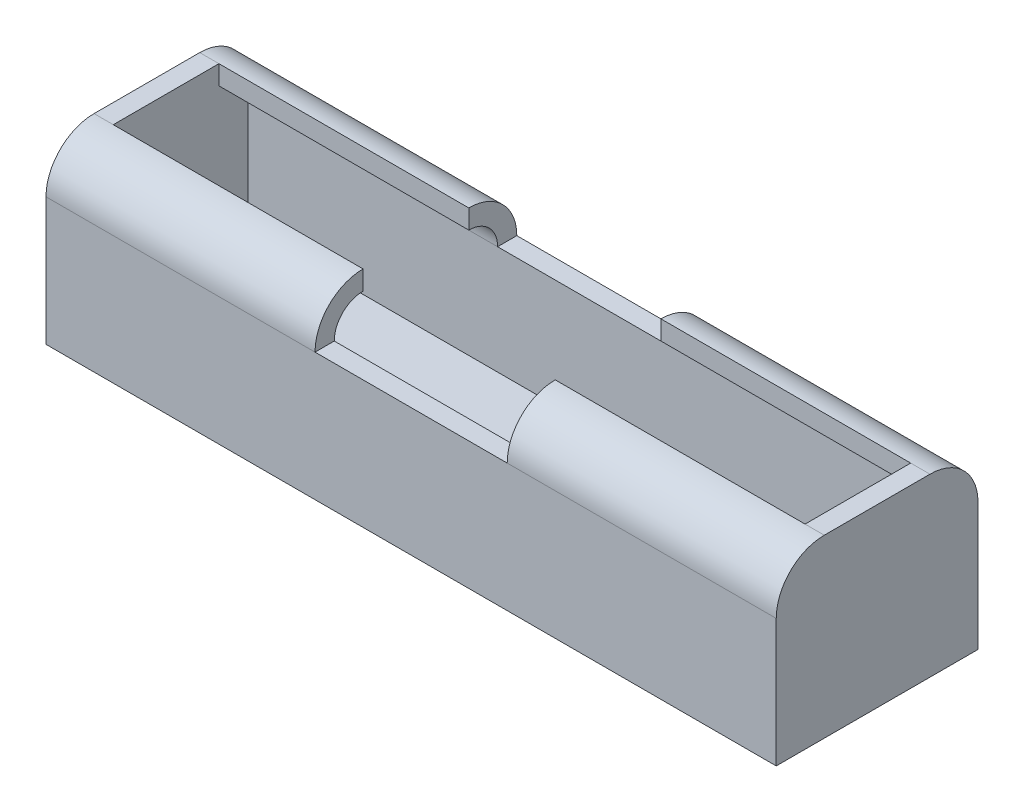
SolidWorks part; units mm, degrees
ref_plane "Front Plane" through (0, 0, 0) normal (0, 0, 1) x (1, 0, 0)
ref_plane "Top Plane" through (0, 0, 0) normal (0, 1, 0) x (1, 0, 0)
ref_plane "Right Plane" through (0, 0, 0) normal (1, 0, 0) x (0, 0, -1)
sketch "Sketch1" plane through (0, 0, 0) normal (1, 0, 0) x (0, 0, -1)
  line L1 (10.5, -9.15) -> (-10.5, -9.15)
  line L2 (10.5, -9.15) -> (10.5, 4.15)
  line L3 (5.5, 9.15) -> (-5.5, 9.15)
  line L4 (-10.5, -9.15) -> (-10.5, 4.15)
  line L5 (10.5, -9.15) -> (-10.5, 9.15) construction
  line L6 (10.5, 9.15) -> (-10.5, -9.15) construction
  arc A0 (10.5, 4.15) -> (5.5, 9.15) centre (5.5, 4.15) ccw
  arc A1 (-5.5, 9.15) -> (-10.5, 4.15) centre (-5.5, 4.15) ccw
  point P0 (0, 0)
  dimension "D3" = 5
  dimension "D1" = 21
  dimension "D2" = 18.3
extrude "Body" add sketch "Sketch1" along normal mid plane 76
shell "Shell1" thickness 2 removed face at (0, 9.15, 0)
sketch "Sketch2" plane through (0, 0, 0) normal (0, 0, 1) x (1, 0, 0)
  line L0 (36, 9.15) -> (-36, 9.15) construction
  line L1 (-10, 4.15) -> (10, 4.15)
  line L2 (-10, 4.15) -> (-10, 9.15)
  line L3 (-10, 9.15) -> (10, 9.15)
  line L4 (10, 4.15) -> (10, 9.15)
  line L5 (-10, 4.15) -> (10, 9.15) construction
  line L6 (-10, 9.15) -> (10, 4.15) construction
  point P0 (0, 6.65)
  point P8 (0, 0)
  dimension "D1" = 20
  dimension "D2" = 5
extrude "Hole" cut sketch "Sketch2" against normal through all both and the other way through all
sketch "Sketch3" plane through (0, -7.15, 0) normal (0, 1, 0) x (1, 0, 0)
  circle A0 centre (0, 0) radius 1.75
  point P2 (0, 0)
  dimension "D1" = 3.5
extrude "Fixation_Hole" cut sketch "Sketch3" against normal through all
